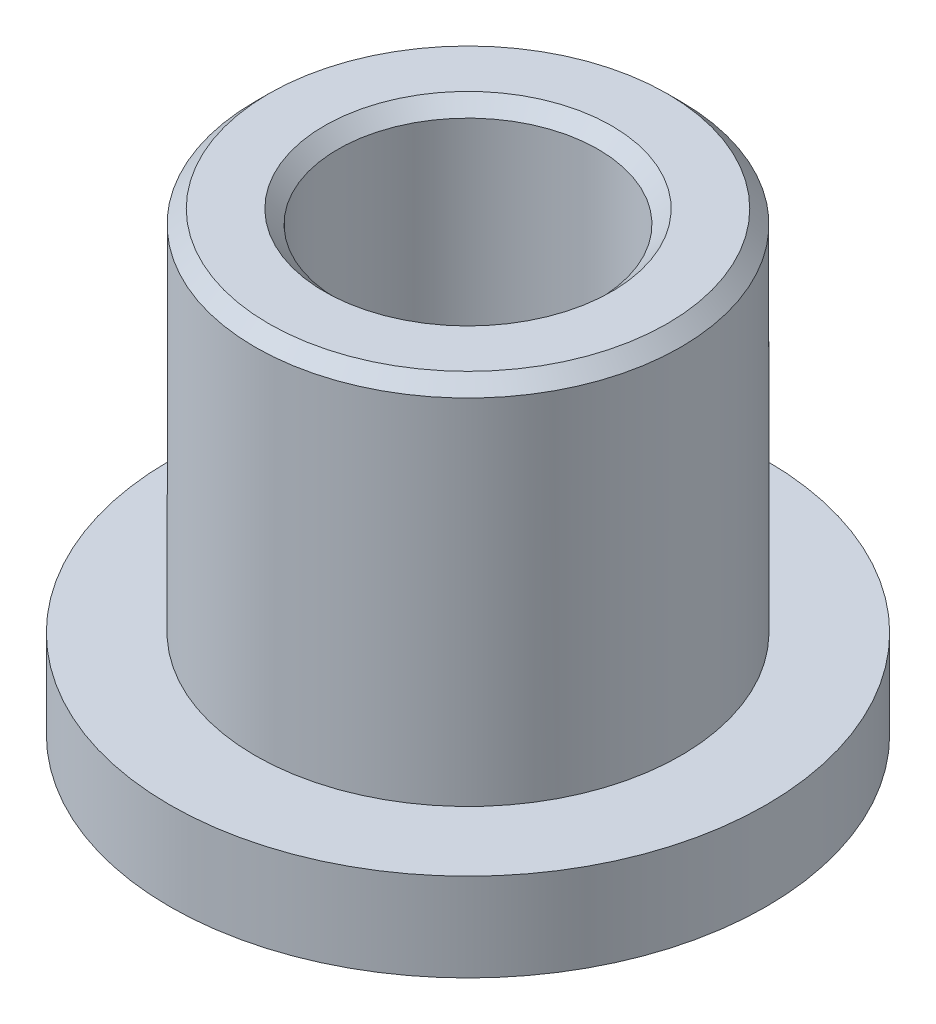
SolidWorks part; units mm, degrees
material "Brass"
ref_plane "Front" through (0, 0, 0) normal (0, 0, 1) x (1, 0, 0)
ref_plane "Top" through (0, 0, 0) normal (0, 1, 0) x (1, 0, 0)
ref_plane "Right" through (0, 0, 0) normal (1, 0, 0) x (0, 0, -1)
ref_axis "side-side" through (80.9, 0, 0) along (-1, 0, 0)
ref_axis "up-down" through (0, 50, 0) along (0, -1, 0)
ref_axis "front-back" through (0, 0, -80.9) along (0, 0, 1)
sketch "Sketch1" plane through (0, 0, 0) normal (0, 0, 1) x (1, 0, 0)
  line L3 (3.925, 1.6256) -> (3.925, 12.4)
  line L7 (5.5, 1.6256) -> (3.925, 1.6256)
  line L11 (5.5, 0) -> (5.5, 1.6256)
  line L15 (3.925, 12.4) -> (2.4, 12.4)
  line L18 (2.4, 0.2) -> (2.4, 12.4)
  line L22 (2.6, 0) -> (2.4, 0.2)
  line L27 (5.5, 0) -> (2.6, 0)
  line L28 (0, 0) -> (0, -3.6079) construction
  dimension "D1" = 1.6256
revolve "Revolve1" add sketch "Sketch1" angle 360 about L28
sketch "Sketch2" plane through (0, 0, 0) normal (0, 0, 1) x (1, 0, 0)
  line L0 (2.4, 12.4) -> (-2.4, 12.4) construction
  line L1 (-7, 16.4) -> (7, 16.4)
  line L2 (-7, 16.4) -> (-7, 8.4)
  line L3 (-7, 8.4) -> (7, 8.4)
  line L4 (7, 16.4) -> (7, 8.4)
  line L5 (0, 0) -> (0, 8.4) construction
  line L6 (5.5, 1.6256) -> (-5.5, 1.6256) construction
  dimension "D1" = 6.7744
  dimension "D2" = 14
  dimension "D3" = 8
  dimension "D4" = 4
extrude "Cut-Extrude1" cut sketch "Sketch2" against normal through all both and the other way through all
chamfer "Chamfer1" distance 0.25 angle 45 2 edges at (0, 8.4, -2.4) (0, 8.4, -3.925)
